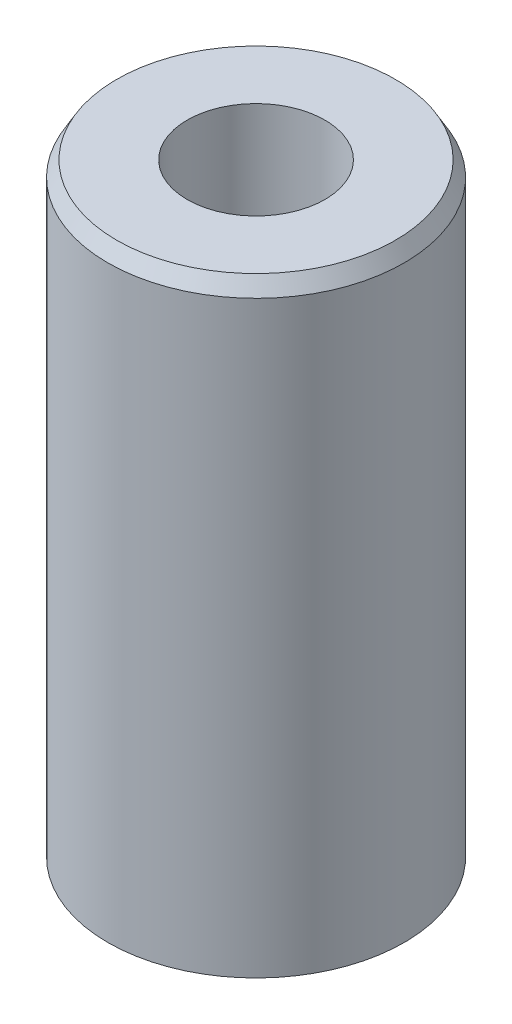
SolidWorks part; units mm, degrees
ref_plane "Front Plane" through (0, 0, 0) normal (0, 0, 1) x (1, 0, 0)
ref_plane "Top Plane" through (0, 0, 0) normal (0, 1, 0) x (1, 0, 0)
ref_plane "Right Plane" through (0, 0, 0) normal (1, 0, 0) x (0, 0, -1)
sketch "Sketch1" plane through (0, 0, 0) normal (0, 1, 0) x (1, 0, 0)
  circle A0 centre (0, 0) radius 40
  dimension "SHAFT_OD" = 80
extrude "Boss-Extrude1" add sketch "Sketch1" along normal blind 165.3879
sketch "Sketch2" plane through (0, 0, 0) normal (0, 1, 0) x (1, 0, 0)
  circle A0 centre (0, 0) radius 18.5968
  dimension "BORE_D" = 37.1937
extrude "Cut-Extrude1" cut sketch "Sketch2" along normal through all
chamfer "Chamfer1" distance 4.1098 angle 30 2 edges at (0, 165.3879, 40) (0, 0, 40) first distance on face at (0, 165.3879, 40) first distance on face at (0, 0, 18.5968)
